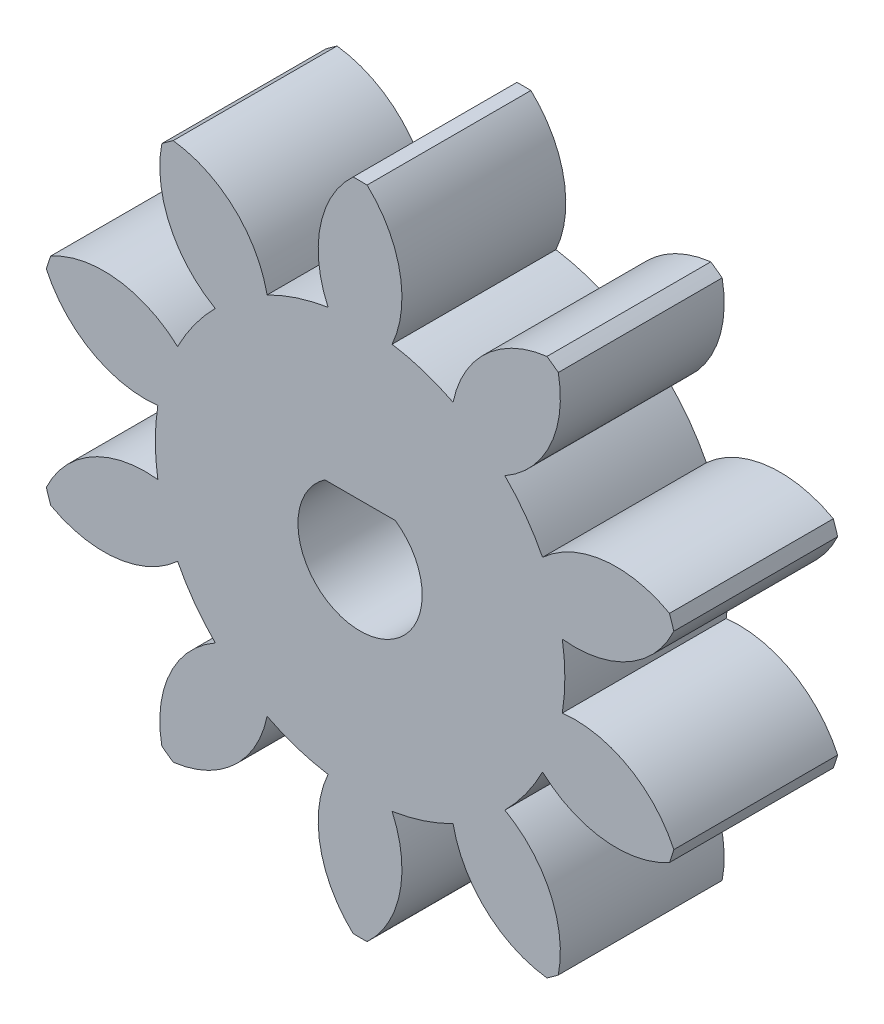
SolidWorks part; units mm, degrees
ref_plane "Front Plane" through (0, 0, 0) normal (0, 0, 1) x (1, 0, 0)
ref_plane "Top Plane" through (0, 0, 0) normal (0, 1, 0) x (1, 0, 0)
ref_plane "Right Plane" through (0, 0, 0) normal (1, 0, 0) x (0, 0, -1)
sketch "Sketch4" plane through (0, 0, 0) normal (0, 0, 1) x (1, 0, 0)
  point P0 (0, 12)
  arc B0 (11.3307, 3.9517) -> (6.6819, 3.404) centre (9.3858, 0.4563) ccw
  arc B1 (6.6819, 3.404) -> (5.3022, 5.303) centre (0, 0) ccw
  arc B2 (5.3022, 5.303) -> (7.2596, 9.555) centre (3.3343, 8.7855) ccw
  arc B3 (7.2596, 9.555) -> (6.844, 9.857) centre (0, 0) ccw
  arc B4 (6.844, 9.857) -> (3.405, 6.6814) centre (7.3251, 5.886) ccw
  arc B5 (3.405, 6.6814) -> (1.1725, 7.4068) centre (0, 0) ccw
  arc B6 (1.1725, 7.4068) -> (0.2569, 11.9973) centre (-2.4664, 9.0675) ccw
  arc B7 (0.2569, 11.9973) -> (-0.2569, 11.9973) centre (0, 0) ccw
  arc B8 (-0.2569, 11.9973) -> (-1.1725, 7.4068) centre (2.4664, 9.0675) ccw
  arc B9 (-1.1725, 7.4068) -> (-3.405, 6.6814) centre (0, 0) ccw
  arc B10 (-3.405, 6.6814) -> (-6.844, 9.857) centre (-7.3251, 5.886) ccw
  arc B11 (-6.844, 9.857) -> (-7.2596, 9.555) centre (0, 0) ccw
  arc B12 (-7.2596, 9.555) -> (-5.3022, 5.303) centre (-3.3343, 8.7855) ccw
  arc B13 (-5.3022, 5.303) -> (-6.6819, 3.404) centre (0, 0) ccw
  arc B14 (-6.6819, 3.404) -> (-11.3307, 3.9517) centre (-9.3858, 0.4563) ccw
  arc B15 (-11.3307, 3.9517) -> (-11.4894, 3.463) centre (0, 0) ccw
  arc B16 (-11.4894, 3.463) -> (-7.4066, 1.1737) centre (-7.8615, 5.1477) ccw
  arc B17 (-7.4066, 1.1737) -> (-7.4066, -1.1737) centre (0, 0) ccw
  arc B18 (-7.4066, -1.1737) -> (-11.4894, -3.463) centre (-7.8615, -5.1477) ccw
  arc B19 (-11.4894, -3.463) -> (-11.3307, -3.9517) centre (0, 0) ccw
  arc B20 (-11.3307, -3.9517) -> (-6.6819, -3.404) centre (-9.3858, -0.4563) ccw
  arc B21 (-6.6819, -3.404) -> (-5.3022, -5.303) centre (0, 0) ccw
  arc B22 (-5.3022, -5.303) -> (-7.2596, -9.555) centre (-3.3343, -8.7855) ccw
  arc B23 (-7.2596, -9.555) -> (-6.844, -9.857) centre (0, 0) ccw
  arc B24 (-6.844, -9.857) -> (-3.405, -6.6814) centre (-7.3251, -5.886) ccw
  arc B25 (-3.405, -6.6814) -> (-1.1725, -7.4068) centre (0, 0) ccw
  arc B26 (-1.1725, -7.4068) -> (-0.2569, -11.9973) centre (2.4664, -9.0675) ccw
  arc B27 (-0.2569, -11.9973) -> (0.2569, -11.9973) centre (0, 0) ccw
  arc B28 (0.2569, -11.9973) -> (1.1725, -7.4068) centre (-2.4664, -9.0675) ccw
  arc B29 (1.1725, -7.4068) -> (3.405, -6.6814) centre (0, 0) ccw
  arc B30 (3.405, -6.6814) -> (6.844, -9.857) centre (7.3251, -5.886) ccw
  arc B31 (6.844, -9.857) -> (7.2596, -9.555) centre (0, 0) ccw
  arc B32 (7.2596, -9.555) -> (5.3022, -5.303) centre (3.3343, -8.7855) ccw
  arc B33 (5.3022, -5.303) -> (6.6819, -3.404) centre (0, 0) ccw
  arc B34 (6.6819, -3.404) -> (11.3307, -3.9517) centre (9.3858, -0.4563) ccw
  arc B35 (11.3307, -3.9517) -> (11.4894, -3.463) centre (0, 0) ccw
  arc B36 (11.4894, -3.463) -> (7.4066, -1.1737) centre (7.8615, -5.1477) ccw
  arc B37 (7.4066, -1.1737) -> (7.4066, 1.1737) centre (0, 0) ccw
  arc B38 (7.4066, 1.1737) -> (11.4894, 3.463) centre (7.8615, 5.1477) ccw
  arc B39 (11.4894, 3.463) -> (11.3307, 3.9517) centre (0, 0) ccw
  circle B40 centre (0, 0) radius 2
sketch_block_instance "Block3-1"
sketch_block "Block3"
extrude "Boss-Extrude3" add sketch "Sketch4" along normal blind 6
sketch "Sketch6" plane through (0, 0, 6) normal (0, 0, 1) x (1, 0, 0)
  circle A0 centre (0, 0) radius 3.2769
extrude "Boss-Extrude4" add sketch "Sketch6" against normal up to surface (6 mm away) up to face at (0, 0, 0)
sketch "Sketch7" plane through (0, 0, 6) normal (0, 0, 1) x (1, 0, 0)
  line L3 (-1.2884, 1.875) -> (1.2884, 1.875)
  arc A0 (-1.2884, 1.875) -> (1.2884, 1.875) centre (0, 0) ccw
  point P0 (0, 0)
  dimension "D2" = 4.55
extrude "Cut-Extrude1" cut sketch "Sketch7" against normal blind 10
